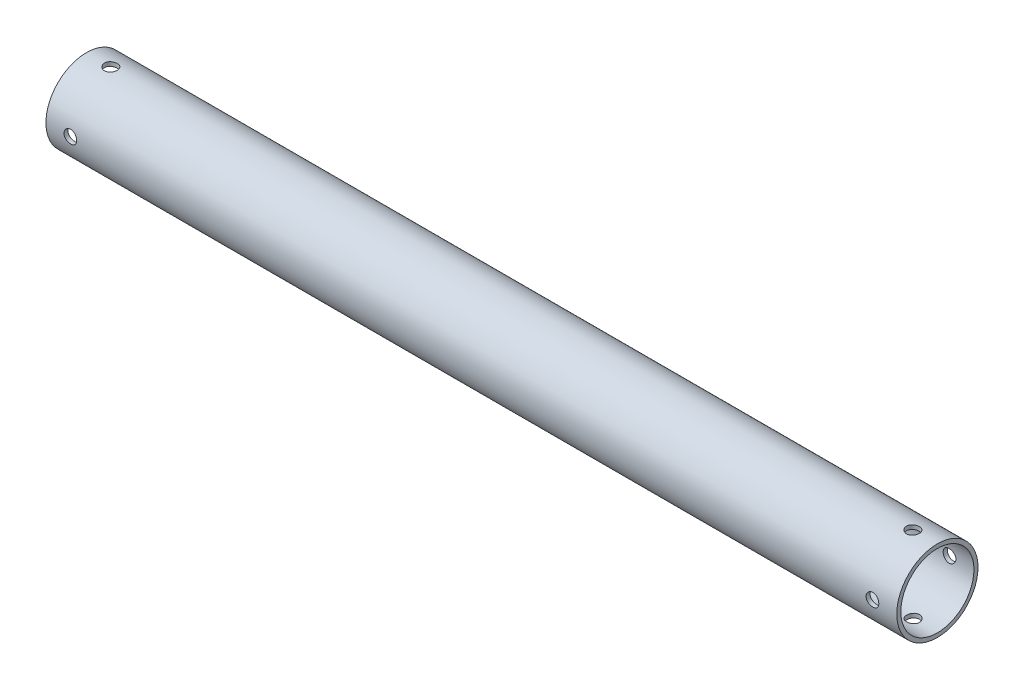
SolidWorks part; units mm, degrees
material "PC High Viscosity"
ref_plane "Front Plane" through (0, 0, 0) normal (0, 0, 1) x (1, 0, 0)
ref_plane "Top Plane" through (0, 0, 0) normal (0, 1, 0) x (1, 0, 0)
ref_plane "Right Plane" through (0, 0, 0) normal (1, 0, 0) x (0, 0, -1)
sketch "Sketch1" plane through (0, 0, 0) normal (1, 0, 0) x (0, 0, -1)
  circle A0 centre (0, 0) radius 15.875
  dimension "D1" = 31.75
extrude "Extrude-Thin1" add sketch "Sketch1" along normal mid plane 332.5813 thin thin type one direction reverse wall 1.5875
sketch "Sketch2" plane through (0, 0, 0) normal (0, 0, 1) x (1, 0, 0)
  line L0 (-166.2906, -15.875) -> (166.2906, -15.875) construction
  line L1 (104.0156, -15.875) -> (125.0156, -15.875)
  line L2 (104.0156, -15.875) -> (104.0156, 15.875)
  line L3 (104.0156, 15.875) -> (125.0156, 15.875)
  line L4 (125.0156, -15.875) -> (125.0156, 15.875)
  line L5 (166.2906, 15.875) -> (-166.2906, 15.875) construction
  line L6 (166.2906, -15.875) -> (166.2906, 15.875) construction
  line L7 (0, 0) -> (0, 11.1276) construction
  line L8 (-125.0156, -15.875) -> (-125.0156, 15.875)
  line L9 (-104.0156, 15.875) -> (-125.0156, 15.875)
  line L10 (-104.0156, -15.875) -> (-104.0156, 15.875)
  line L11 (-104.0156, -15.875) -> (-125.0156, -15.875)
  line L13 (166.2906, -15.875) -> (163.9665, -15.875)
  line L14 (166.2906, -15.875) -> (166.2906, 15.875)
  line L15 (166.2906, 15.875) -> (163.9665, 15.875)
  line L16 (163.9665, -15.875) -> (163.9665, 15.875)
  dimension "D1" = 41.275
  dimension "D2" = 21
  dimension "D3" = 2.3241
sketch "Sketch3" plane through (0, 0, 0) normal (0, 0, 1) x (1, 0, 0)
  line L0 (-166.2906, 15.875) -> (-166.2906, -15.875) construction
  line L1 (166.2906, -15.875) -> (166.2906, 15.875) construction
  circle A0 centre (-156.7656, 0) radius 2.4892
  circle A1 centre (156.7656, 0) radius 2.4892
  dimension "D1" = 4.9784
  dimension "D2" = 9.525
  dimension "D3" = 9.525
extrude "Cut-Extrude1" cut sketch "Sketch3" against normal through all both and the other way through all
sketch "Sketch4" plane through (0, 0, 0) normal (0, 1, 0) x (1, 0, 0)
  line L0 (-166.2906, 15.875) -> (-166.2906, -15.875) construction
  line L1 (166.2906, -15.875) -> (166.2906, 15.875) construction
  circle A0 centre (156.7656, 0) radius 2.4892
  circle A1 centre (-156.7656, 0) radius 2.4892
  dimension "D1" = 4.9784
  dimension "D2" = 9.525
  dimension "D3" = 9.525
extrude "Cut-Extrude2" cut sketch "Sketch4" against normal through all both and the other way through all
equation "\"D2@Sketch2\"=21mm"
